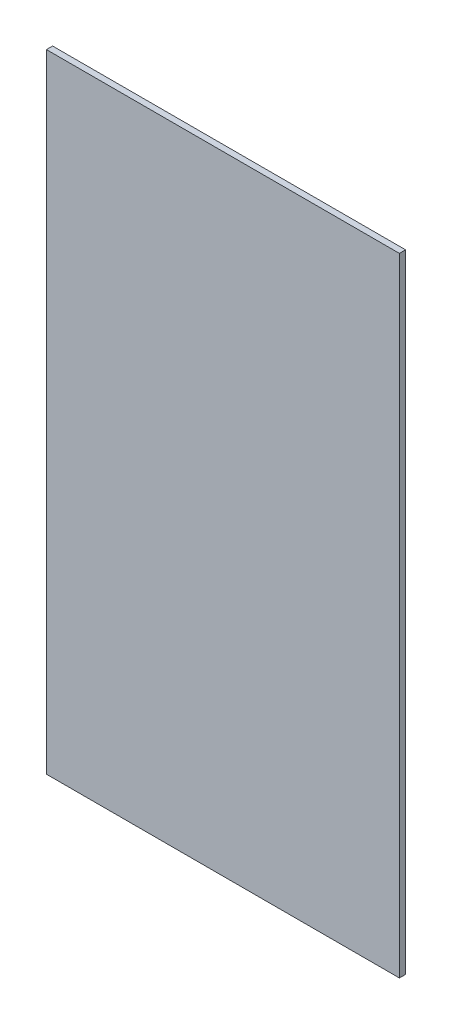
SolidWorks part; units mm, degrees
ref_plane "Front Plane" through (0, 0, 0) normal (0, 0, 1) x (1, 0, 0)
ref_plane "Top Plane" through (0, 0, 0) normal (0, 1, 0) x (1, 0, 0)
ref_plane "Right Plane" through (0, 0, 0) normal (1, 0, 0) x (0, 0, -1)
sketch "Sketch1" plane through (0, 0, 0) normal (0, 0, 1) x (1, 0, 0)
  line L1 (0, 0) -> (57.15, 0)
  line L2 (0, 0) -> (0, 101.6)
  line L3 (0, 101.6) -> (57.15, 101.6)
  line L4 (57.15, 0) -> (57.15, 101.6)
  dimension "D1" = 101.6
  dimension "D2" = 57.15
extrude "Boss-Extrude1" add sketch "Sketch1" along normal blind 1
